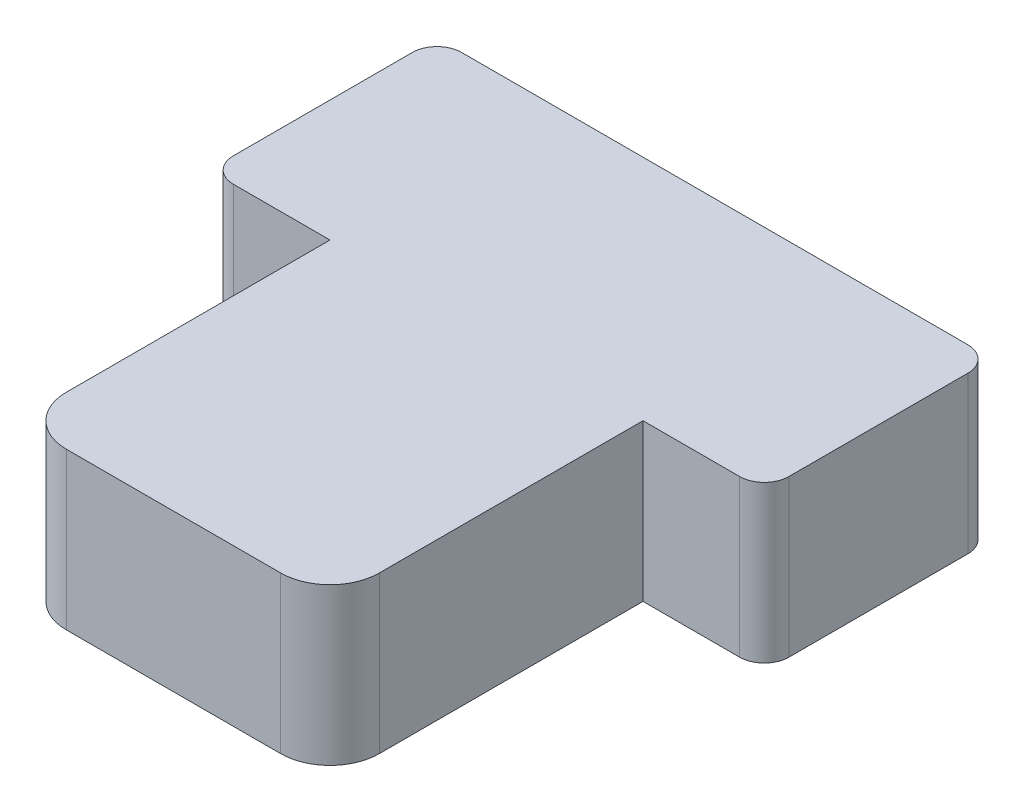
SolidWorks part; units mm, degrees
material "Beech"
ref_plane "Front Plane" through (0, 0, 0) normal (0, 0, 1) x (1, 0, 0)
ref_plane "Top Plane" through (0, 0, 0) normal (0, 1, 0) x (1, 0, 0)
ref_plane "Right Plane" through (0, 0, 0) normal (1, 0, 0) x (0, 0, -1)
sketch "Sketch1" plane through (0, 0, 0) normal (0, 1, 0) x (1, 0, 0)
  line L0 (0, 0) -> (6.35, 0)
  line L1 (0, 0) -> (0, 6.35)
  line L2 (6.35, 0) -> (6.35, 6.35)
  line L4 (-2.46, 10.9807) -> (-2.46, 6.35)
  line L5 (-2.46, 10.9807) -> (8.81, 10.9807)
  line L6 (-2.46, 6.35) -> (0, 6.35)
  line L7 (8.81, 10.9807) -> (8.81, 6.35)
  line L8 (6.35, 6.35) -> (8.81, 6.35)
  dimension "D1" = 6.35
  dimension "D2" = 6.35
  dimension "D3" = 11.27
  dimension "D4" = 4.6307
extrude "MotorSupport_Extrude" add sketch "Sketch1" along normal blind 3.175
fillet "MotorSupport_BottomFillet" radius 1 2 edges at (0, 1.5875, 0) (6.35, 1.5875, 0)
fillet "MotorSupport_TopFillet" radius 0.5 4 edges at (-2.46, 1.5875, -6.35) (-2.46, 1.5875, -10.9807) (8.81, 1.5875, -10.9807) (8.81, 1.5875, -6.35)
equation "\"CageLeftBottomEdge\"=22.11mm"
equation "\"CageLeftTopEdge\"=22.11mm"
equation "\"CageRightBottomEdge\"=21.63mm"
equation "\"CageRightTopEdge\"=21.63mm"
equation "\"CageHeight\"=86.04mm"
equation "\"CageLength\"=73.76mm"
equation "\"CageTopScrewClearance\"=10mm"
equation "\"CageBottomScrewClearance\"=25mm"
equation "\"CageLeftTopDepth\"= 11.65mm"
equation "\"CageLeftBottomDepth\"=11.11mm"
equation "\"CageLeftTopHeight\"=8.56175mm"
equation "\"CageLeftBottomHeight\"=16mm"
equation "\"CageRightTopDepth\"= 11.05mm"
equation "\"CageRightBottomDepth\"=10.58mm"
equation "\"CageRightTopHeight\"=9.6mm"
equation "\"CageRightBottomHeight\"=15.49mm"
equation "\"CageLeftTopChannelDepth\"=2.41908mm"
equation "\"CageLeftBottomChannelDepth\"=2.588mm"
equation "\"CageLeftChannelHeight\"=11.7mm"
equation "\"CageRightTopChannelDepth\"=2.32mm"
equation "\"CageRightBottomChannelDepth\"=2.318mm"
equation "\"CageRightChannelHeight\"=10mm"
equation "\"CageChanRelHeight\"=23.99mm"
equation "\"CageChanRelDepth\"=5.492mm"
equation "\"CageChamberRadius\"=16.261mm"
equation "\"CageScrewDiameter\"=4.8mm"
equation "\"CageSetScrewDiameter\"=3.5mm"
equation "\"CageAxleRadius\"=6.639mm"
equation "\"CageAxleKeyHeight\"=1.619mm"
equation "\"CageAxleKeyWidth\"=2.662mm"
equation "\"CageHoseWindowWidth\"=16.29mm"
equation "\"CageHoseWindowHeight\"=26.5mm"
equation "\"CageHoseWindow-Edge\"=8.89mm"
equation "\"CageScrew-VerticalEdge\"=5.0mm"
equation "\"CageScrew-HorizontalEdge\"=7.5mm"
equation "\"CageScrew-HoseCornerScrewEdge\"=4.45mm"
equation "\"CageAxle-BottomEdge\"=56.05mm"
equation "\"CageAxle-FrontEdge\"=46.03mm"
equation "\"CageBackSetScrew-Axle\"=40mm"
equation "\"CageFrontSetScrew-Axle\"=22mm"
equation "\"CageVelocityWindow-BackEdge\"=34.8mm"
equation "\"CageVelocityWindow-BottomEdge\"=27.55mm"
equation "\"CageVelocityWindowHeight\"=22.29mm"
equation "\"CageVelocityWindowWidth\"=12.61mm"
equation "\"TriggerSlot-BottomEdge\"=6.35mm"
equation "\"TriggerSlot-FrontEdge\"=15mm"
equation "\"TriggerSlotSize\"=6.7mm"
equation "\"TriggerRackOffset\"=.236224in"
equation "\"TriggerSlotSizeInt\"=.25in"
equation "\"MotorMountLegLength\"=.25in"
equation "\"GearOffset\"=.264907in"
equation "\"TriggerSlotSpacing\"=.25in"
equation "\"TGMGearFaceDiameter\"=24.40mm"
equation "\"TGMCylinderLength\"=15.00mm"
equation "\"TGMScrewHole-Center\"=8.70mm"
equation "\"TGMScrewHoleDiameter\"=5.04mm"
equation "\"TGMCenterHoleDiameter\"=9.50mm"
equation "\"TGMShaftCollarSideLength\"=19.00mm"
equation "\"TGMShaftCollarDockingDepth\"=7.00mm"
equation "\"whitemotordepth\"=11.27mm"
equation "\"whitemotorbackdepth\"=3.845mm"
equation "\"whitemotoraxledepth\" = 3.5mm"
equation "\"whitemotoraxleoffset\"=11.4mm"
equation "\"whitemotorwidth\"=12.07mm"
equation "\"whitemotorheight\"=16.68mm"
equation "\"whitemotorcylinderlength\" =13.04mm"
equation "\"whitemotorcylinderradius\"=3.845mm"
equation "\"whitemotorcylinderoffset\"=2.35mm"
equation "\"whitemotorcutoutlength\"=1.88mm"
equation "\"whitemotorouterrad\"=5mm"
equation "\"whitemotorinnerrad\"=2.95mm"
equation "\"D1@Sketch1\"=\"TriggerSlotSizeInt\""
equation "\"D2@Sketch1\"=\"MotorMountLegLength\""
equation "\"D3@Sketch1\"=\"whitemotordepth\""
equation "\"D4@Sketch1\"=\"GearOffset\"+\"TriggerRackOffset\"-\"whitemotoraxleoffset\"+\"elasticdepth\"+.005in"
equation "\"D1@MotorSupport_Extrude\"=.125in"
equation "\"TriggerMiniSlotWidth\"=3.5mm"
equation "\"TriggerRackWidth\"=6.5mm"
equation "\"elasticracklength\"=2in"
equation "\"elasticrackpegsize\"=.25in"
equation "\"elasticrackpegbuffer\"=.125in"
equation "\"elasticrackpegspacing\"=1.76476378in"
equation "\"elasticbaybuffer\"=.25in"
equation "\"elasticdepth\"=.125in"
equation "\"elasticbaydepth\"=.75in"
equation "\"motormountwidth\"=12mm"
equation "\"motormountcornerfillet\"=3mm"
equation "\"pandiscradius\"=14in"
equation "\"towermaterialwidth\"=.25in"
equation "\"towerslotlength\"=.5in"
equation "\"towermarkerspace\"=5in"
equation "\"towerslothorizoffset\"=1in"
equation "\"towerslothorizspacing\"=2in"
equation "\"towerslotvertoffset\"=3in"
equation "\"towerslotvertspacing\"=2in"
equation "\"towerheight\"=12in"
equation "\"towerupslot\"=1in"
equation "\"toweraxle\"=.5in"
equation "\"towerplatslotoffset\"=1.5in"
equation "\"towermotorpanelheight\"=10in"
equation "\"towerplatdepth\"=2in"
equation "\"stepperouterrad\"=10mm"
equation "\"stepperscrewsize\"=3.45mm"
equation "\"stepperscrewc2c\"=49.5mm"
equation "\"stepperdepthoffset\"=24mm"
equation "\"stepperhorizoffset\"=22.91mm"
